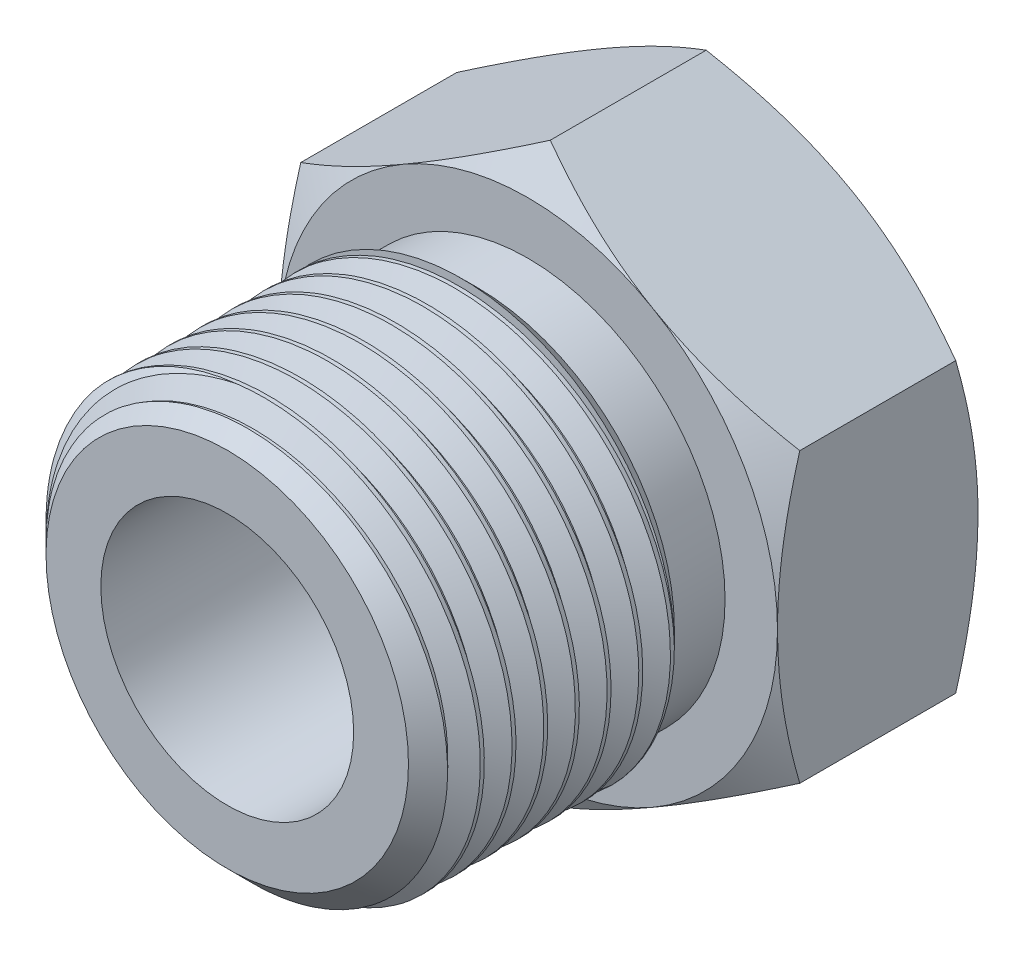
SolidWorks part; units mm, degrees
ref_plane "Front Plane" through (0, 0, 0) normal (0, 0, 1) x (1, 0, 0)
ref_plane "Top Plane" through (0, 0, 0) normal (0, 1, 0) x (1, 0, 0)
ref_plane "Right Plane" through (0, 0, 0) normal (1, 0, 0) x (0, 0, -1)
sketch "Sketch1" plane through (0, 0, 0) normal (1, 0, 0) x (0, 0, -1)
  line L0 (14.351, 0) -> (-14.351, 0) construction
  line L1 (14.351, 14.2875) -> (14.351, -14.2875) construction
  line L2 (-14.351, 7.239) -> (-14.351, -7.239) construction
  line L3 (-14.351, 12.192) -> (-14.351, -12.192) construction
  line L4 (-14.351, 12.192) -> (-12.5367, 12.192) construction
  point P4 (0, 0)
  point P7 (14.351, 0)
  point P11 (-14.351, 0)
  point P14 (-14.351, 0)
ref_plane "Plane1" through (0, 0, -14.351) normal (0, 0, 1) x (1, 0, 0)
sketch "Sketch2" plane through (0, 0, -14.351) normal (0, 0, 1) x (1, 0, 0)
  line L0 (0, 14.2875) -> (0, -14.2875) construction
  line L1 (0, 16.4978) -> (-14.2875, 8.2489)
  line L2 (-14.2875, 8.2489) -> (-14.2875, -8.2489)
  line L3 (-14.2875, -8.2489) -> (0, -16.4978)
  line L4 (0, -16.4978) -> (14.2875, -8.2489)
  line L5 (14.2875, -8.2489) -> (14.2875, 8.2489)
  line L6 (14.2875, 8.2489) -> (0, 16.4978)
  circle A0 centre (0, 0) radius 14.2875 construction
  dimension "D1" = 28.575
extrude "Boss-Extrude1" add sketch "Sketch2" along normal blind 11.4808
sketch "Sketch3" plane through (0, 0, -2.8702) normal (0, 0, 1) x (1, 0, 0)
  circle A0 centre (0, 0) radius 12.192
  dimension "D1" = 24.384
extrude "Boss-Extrude2" add sketch "Sketch3" along normal up to vertex (17.2212 mm away) up to point (0, 0, 14.351)
sketch "Sketch4" plane through (0, 0, 14.351) normal (0, 0, 1) x (1, 0, 0)
  circle A0 centre (0, 0) radius 7.239
  dimension "D1" = 14.478
extrude "Cut-Extrude1" cut sketch "Sketch4" against normal through all
chamfer "Chamfer1" distance 1.8143 angle 45 1 edges at (12.192, 0, 14.351)
sketch "Sketch6" plane through (0, 0, -14.351) normal (0, 0, -1) x (-1, 0, 0)
  line L0 (0, 14.2875) -> (0, -14.2875) construction
  line L1 (0, 16.4978) -> (14.2875, 8.2489) construction
  circle A0 centre (0, 0) radius 14.2875
extrude "Cut-Extrude3" cut sketch "Sketch6" against normal blind 2.54 draft 60 flip side to cut
sketch "Sketch7" plane through (0, 0, -2.8702) normal (0, 0, 1) x (1, 0, 0)
  line L0 (0, 16.4978) -> (-14.2875, 8.2489) construction
  circle A0 centre (0, 0) radius 14.2875
extrude "Cut-Extrude4" cut sketch "Sketch7" against normal blind 2.54 draft 60 flip side to cut
sketch "Sketch12" plane through (0, 0, 0) normal (1, 0, 0) x (0, 0, -1)
  line L0 (-0.9398, 12.192) -> (-0.0327, 11.2849)
  line L1 (2.8702, 12.192) -> (-0.9398, 12.192)
  line L2 (2.8702, 12.192) -> (2.8702, 11.2849)
  line L3 (2.8702, 11.2849) -> (-0.9398, 11.2849)
  line L4 (-0.9398, 12.192) -> (-0.9398, 11.2849)
  dimension "D1" = 3.81
  dimension "D2" = 0.9071
  dimension "D3" = 45
revolve "Cut-Revolve1" cut sketch "Sketch12" angle 360 about L0 region at (0, 11.7589, -1.1818)
sketch "Sketch8" plane through (0, 0, 0) normal (1, 0, 0) x (0, 0, -1)
  line L0 (-12.5367, -12.192) -> (-0.9398, -12.192) construction
  line L1 (-14.351, 10.3777) -> (-14.351, -10.3777) construction
  point P0 (-10.7224, -12.192)
  dimension "D1" = 3.6286
ref_plane "Plane3" through (0, 0, 0.9398) normal (0, 0, 1) x (1, 0, 0)
split "Split2" trim tools "Plane3" bodies to split 162 154 resulting bodies 155 156
sketch "Sketch10" plane through (0, 0, 0.9398) normal (0, 0, -1) x (-1, 0, 0)
  circle A1 centre (0, 0) radius 12.192
  dimension "D1" = 24.384
curve "Helix/Spiral1" pitch 1.8143 height 25.4 radius 12.192 centre (0, 0, 0.9398) axis (0, 0, 1) start towards (1, 0, 0)
sketch "Sketch11" plane through (0, 0, 0) normal (1, 0, 0) x (0, 0, -1)
  line L0 (-1.5068, 12.3884) -> (0.3075, 12.3884) construction
  line L1 (0.3075, 12.3884) -> (-0.5996, 10.8172) construction
  line L2 (-0.5996, 10.8172) -> (-1.5068, 12.3884) construction
  line L3 (-0.713, 11.0136) -> (-0.4862, 11.0136) construction
  line L4 (-0.5996, 12.3884) -> (-0.5996, 12.192) construction
  line L5 (-1.3934, 12.192) -> (0.1941, 12.192) construction
  line L6 (-0.5996, 11.0136) -> (-0.5996, 10.8172) construction
  line L7 (-0.5996, 12.2902) -> (-1.4501, 12.2902) construction
  line L8 (-1.4501, 12.2902) -> (-0.713, 11.0136)
  line L9 (-0.713, 11.0136) -> (-0.4862, 11.0136)
  line L10 (-0.4862, 11.0136) -> (0.3075, 12.3884)
  line L11 (0.3075, 12.3884) -> (-1.4501, 12.2902)
  dimension "D1" = 1.8143
  dimension "D2" = 0.2268
sweep "Cut-Sweep1" cut profiles "Sketch11" path "Helix/Spiral1" align with end faces yes
combine bodies "Combine2" operation type add bodies to combine 161 156
equation "\"D1@Sketch2\"=\"Hex@Sketch1\""
equation "\"D1@Boss-Extrude1\"=\"Length@Sketch1\"*.4"
equation "\"D1@Sketch3\"=\"Thread@Sketch1\""
equation "\"D1@Sketch4\"=\"Thru@Sketch1\""
equation "\"D1@Chamfer1\"=\"Pitch@Sketch1\""
equation "\"D1@Sketch8\"=\"Pitch@Sketch1\"*2"
equation "\"D4@Helix/Spiral1\"=\"Pitch@Sketch1\""
equation "\"D1@Sketch11\"=\"Pitch@Sketch1\""
equation "\"D2@Sketch11\"=\"D1@Sketch11\"*.125"
equation "\"D2@Sketch12\"=\"Pitch@Sketch1\"*.5"
equation "\"D1@Sketch10\"=\"Thread@Sketch1\""
